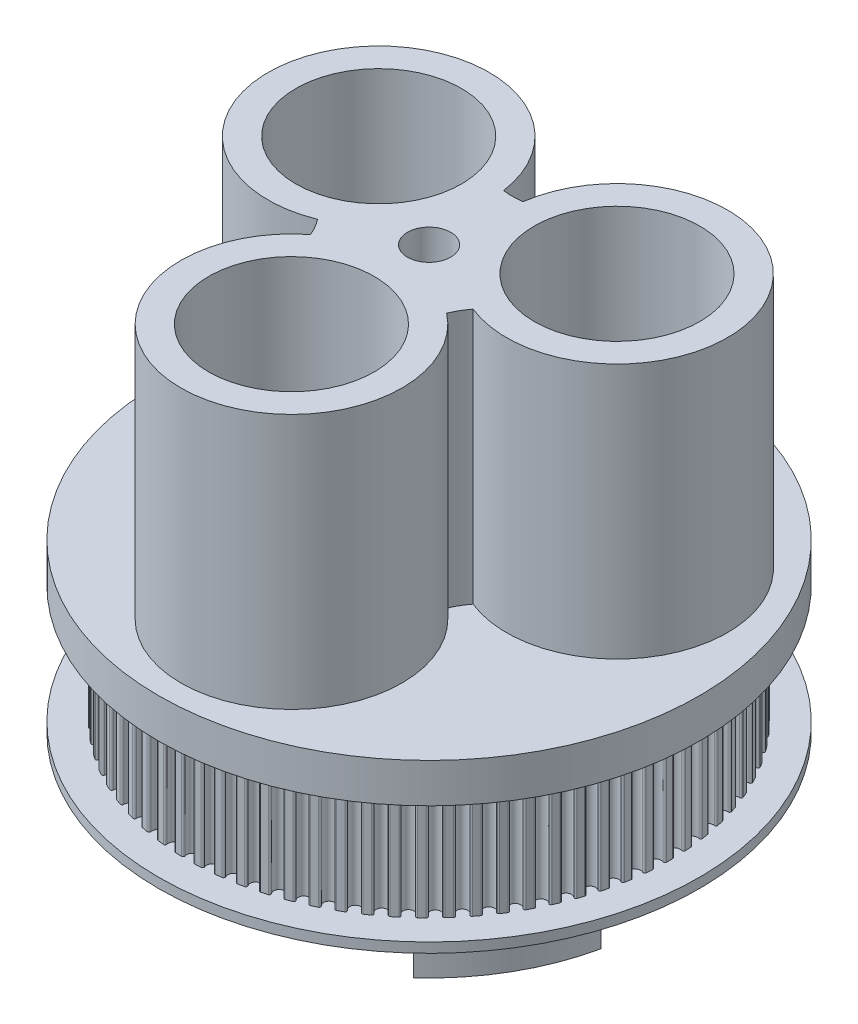
SolidWorks part; units mm, degrees
ref_plane "Front Plane" through (0, 0, 0) normal (0, 0, 1) x (1, 0, 0)
ref_plane "Top Plane" through (0, 0, 0) normal (0, 1, 0) x (1, 0, 0)
ref_plane "Right Plane" through (0, 0, 0) normal (1, 0, 0) x (0, 0, -1)
sketch "Sketch1" plane through (0, 0, 0) normal (0, 1, 0) x (1, 0, 0)
  line L0 (0, -55) -> (0, 55) construction
  circle A0 centre (0, 0) radius 27.5
  circle A1 centre (0, 0) radius 2.2
  circle A2 centre (0, -14) radius 8.425
  circle A3 centre (-12.1244, 7) radius 8.425
  circle A4 centre (12.1244, 7) radius 8.425
  point P14 (0, 0)
  dimension "D1" = 55
  dimension "D2" = 4.4
  dimension "D3" = 16.85
  dimension "D4" = 14
  dimension "D5" = 3
extrude "Boss-Extrude1" add sketch "Sketch1" along normal blind 43
sketch "Sketch4" plane through (0, 0, 0) normal (1, 0, 0) x (0, 0, -1)
  line L0 (-37.5347, 7) -> (42.095, 7) construction
  line L2 (27.5, 0) -> (27.5, 43) construction
  line L3 (27.5, 13) -> (24.5, 13)
  line L4 (27.5, 13) -> (27.5, 1)
  line L5 (27.5, 1) -> (24.5, 1)
  line L6 (24.5, 13) -> (24.5, 1)
  line L7 (0, 27.0195) -> (0, 5.2114) construction
  line L8 (0, 55) -> (0, -55) construction
  line L9 (55, 0) -> (-55, 0) construction
  dimension "D1" = 7
  dimension "D2" = 12
  dimension "D3" = 3
revolve "Cut-Revolve1" cut sketch "Sketch4" angle 360 about L7 region at (0, 7, -26)
sketch "Sketch5" plane through (0, 43, 0) normal (0, 1, 0) x (1, 0, 0)
  line L0 (0, 0) -> (23.3129, -13.4597) construction
  line L1 (0, -55) -> (0, 55) construction
  circle A0 centre (12.1244, 7) radius 11.25
  circle A1 centre (0, 0) radius 30
  circle A2 centre (0, -14) radius 11.25
  circle A3 centre (-12.1244, 7) radius 11.25
  circle A4 centre (13.8564, -8) radius 7.5
  circle A5 centre (-13.8564, -8) radius 7.5
  circle A6 centre (0, 16) radius 7.5
  point P12 (0, 0)
  point P22 (0, 0)
  circle M8 centre (0, 0) radius 27.5
  dimension "D1" = 22.5
  dimension "D2" = 60
  dimension "D5" = 15
  dimension "D4" = 60
  dimension "D6" = 16
  dimension "D3" = 3
  dimension "D7" = 3
extrude "Cut-Extrude3" cut sketch "Sketch5" against normal blind 26 contours A6 A0 A4 A2 A5 A3 M8 | A2 A5 A3 | A4 L0 A0 | L0 A4 A2 | A0 A6 A3 region at (16.4258, 43, 6.4713) region at (13.8172, 43, 10.9895) region at (0, 43, -17.4608) region at (-15.1215, 43, 8.7304) region at (-26.7222, 43, 0)
sketch "Sketch6" plane through (0, 0, 0) normal (0, -1, 0) x (1, 0, 0)
  line L0 (0, 0) -> (-24.1185, 13.9248) construction
  line L1 (0, -23.65) -> (0, 23.65) construction
  line L2 (-15.3005, 16.9037) -> (-11.0727, 12.2329)
  line L3 (-22.2893, 4.7988) -> (-16.1304, 3.4728)
  line L4 (15.3005, 16.9037) -> (11.0727, 12.2329)
  line L5 (22.2893, 4.7988) -> (16.1304, 3.4728)
  line L6 (6.9888, -21.7025) -> (5.0577, -15.7057)
  line L7 (-6.9888, -21.7025) -> (-5.0577, -15.7057)
  circle A0 centre (0, 0) radius 22.8 construction
  circle A1 centre (0, 0) radius 27.5 construction
  circle A2 centre (0, 0) radius 16.5
  circle A3 centre (0, 0) radius 22.8
  point P24 (1.3727, -0.446)
  point P26 (0, 0)
  dimension "D1" = 4.7
  dimension "D3" = 6.3
  dimension "D2" = 60
  dimension "D4" = 35.7
  dimension "D5" = 3
extrude "Boss-Extrude2" add sketch "Sketch6" along normal blind 5.5 contours L2 A3 L3 A2 | A3 A2 | A3 A2 region at (-16.8869, 0, 9.7496) region at (16.8869, 0, 9.7496) region at (0, 0, -19.4993)
ref_plane "Plane1" through (0, 13, 0) normal (0, -1, 0) x (-1, 0, 0)
sketch "Sketch9" plane through (0, 13, 0) normal (0, -1, 0) x (-1, 0, 0)
  circle A0 centre (0, 0) radius 24.63 construction
  circle A1 centre (24.0514, -0.9457) radius 0.56
  dimension "D1" = 49.26
  dimension "D2" = 1.12
extrude "Cut-Extrude11" cut sketch "Sketch9" along normal up to surface (12 mm away) up to face at (0, 1, 24.5)
fillet "Fillet1" radius 0.16 2 edges at (-24.4642, 7, 1.3242) (-24.4926, 7, 0.6009)
pattern_circular "CirPattern1" count 78 over 360 about axis through (0, 0, 0) along (0, 1, 0) of "Cut-Extrude11", "Fillet1"
